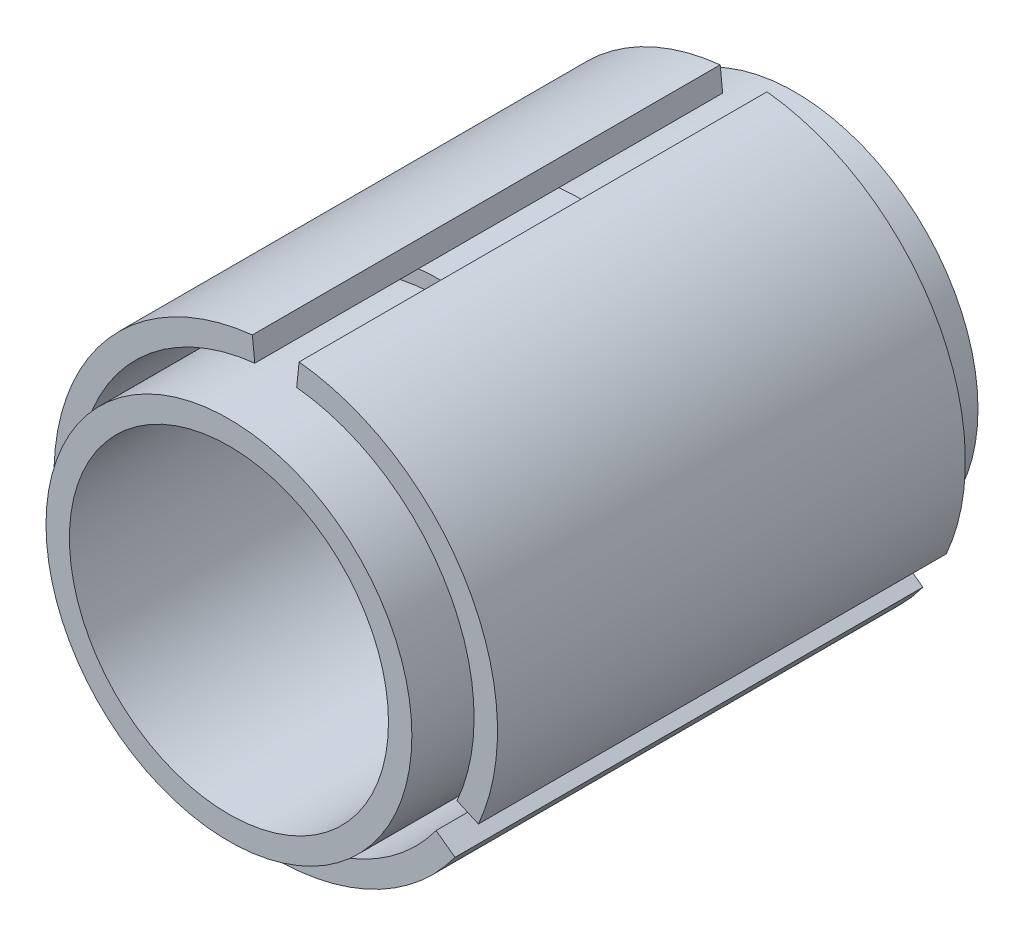
SolidWorks part; units mm, degrees
ref_plane "Alzado" through (0, 0, 0) normal (0, 0, 1) x (1, 0, 0)
ref_plane "Planta" through (0, 0, 0) normal (0, 1, 0) x (1, 0, 0)
ref_plane "Vista lateral" through (0, 0, 0) normal (1, 0, 0) x (0, 0, -1)
sketch "Croquis1" plane through (0, 0, 0) normal (0, 0, 1) x (1, 0, 0)
  circle A0 centre (0, 0) radius 42.4
  dimension "D1" = 84.8
extrude "Saliente-Extruir1" add sketch "Croquis1" along normal mid plane 30
sketch "Croquis2" plane through (0, 0, 0) normal (0, 0, 1) x (1, 0, 0)
  line L0 (0, 0) -> (0, 47.1355) construction
  line L1 (0, 0) -> (-5, 47.1355) construction
  line L2 (0, 0) -> (5, 47.1355) construction
  line L4 (-5, 47.1355) -> (-4.4726, 42.1634)
  line L5 (5, 47.1355) -> (4.4726, 42.1634)
  line L6 (38.3206, -27.8979) -> (34.2783, -24.9551)
  line L7 (43.3206, -19.2376) -> (38.7509, -17.2084)
  line L8 (-43.3206, -19.2376) -> (-38.7509, -17.2084)
  line L9 (-38.3206, -27.8979) -> (-34.2783, -24.9551)
  arc A0 (-5, 47.1355) -> (-43.3206, -19.2376) centre (0, 0) ccw
  circle A1 centre (0, 0) radius 42.4 construction
  arc A2 (-4.4726, 42.1634) -> (-38.7509, -17.2084) centre (0, 0) ccw
  arc A3 (38.7509, -17.2084) -> (4.4726, 42.1634) centre (0, 0) ccw
  arc A4 (43.3206, -19.2376) -> (5, 47.1355) centre (0, 0) ccw
  arc A5 (-38.3206, -27.8979) -> (38.3206, -27.8979) centre (0, 0) ccw
  arc A6 (-34.2783, -24.9551) -> (34.2783, -24.9551) centre (0, 0) ccw
  point P24 (0, 0)
  dimension "D1" = 10
  dimension "D2" = 5
  dimension "D3" = 5
  dimension "D4" = 3
extrude "Saliente-Extruir2" add sketch "Croquis2" along normal mid plane 30
sketch "Croquis3" plane through (0, 0, 0) normal (0, 0, 1) x (1, 0, 0)
  line L0 (-4.4726, 42.1634) -> (-5, 47.1355)
  line L1 (-4.4726, 42.1634) -> (-5, 47.1355) construction
  line L2 (4.4726, 42.1634) -> (5, 47.1355)
  line L3 (38.7509, -17.2084) -> (43.3206, -19.2376)
  line L4 (38.7509, -17.2084) -> (43.3206, -19.2376) construction
  line L5 (38.3206, -27.8979) -> (34.2783, -24.9551)
  line L6 (38.3206, -27.8979) -> (34.2783, -24.9551) construction
  line L7 (-38.3206, -27.8979) -> (-34.2783, -24.9551)
  line L8 (-34.2783, -24.9551) -> (-38.3206, -27.8979) construction
  line L9 (-43.3206, -19.2376) -> (-38.7509, -17.2084)
  line L10 (-43.3206, -19.2376) -> (-38.7509, -17.2084) construction
  arc A0 (-4.4726, 42.1634) -> (-38.7509, -17.2084) centre (0, 0) ccw
  arc A1 (-5, 47.1355) -> (-43.3206, -19.2376) centre (0, 0) ccw
  arc A2 (38.7509, -17.2084) -> (4.4726, 42.1634) centre (0, 0) ccw
  arc A3 (43.3206, -19.2376) -> (5, 47.1355) centre (0, 0) ccw
  arc A4 (-34.2783, -24.9551) -> (34.2783, -24.9551) centre (0, 0) ccw
  arc A5 (-38.3206, -27.8979) -> (38.3206, -27.8979) centre (0, 0) ccw
  dimension "D1" = 84.8
extrude "Saliente-Extruir3" add sketch "Croquis3" along normal mid plane 100
sketch "Croquis4" plane through (0, 0, 0) normal (0, 0, 1) x (1, 0, 0)
  circle A0 centre (0, 0) radius 39.1
  dimension "D1" = 78.2
extrude "Saliente-Extruir4" add sketch "Croquis4" along normal blind 60 and the other way blind 61
sketch "Croquis5" plane through (0, 0, 60) normal (0, 0, 1) x (1, 0, 0)
  circle A0 centre (0, 0) radius 34.1
  dimension "D1" = 68.2
extrude "Cortar-Extruir1" cut sketch "Croquis5" against normal blind 58
sketch "Croquis6" plane through (0, 0, -61) normal (0, 0, -1) x (-1, 0, 0)
  circle A0 centre (0, 0) radius 34.1
  dimension "D1" = 68.2
extrude "Cortar-Extruir2" cut sketch "Croquis6" against normal blind 58
sketch "Croquis7" plane through (0, 0, 0) normal (0, 0, 1) x (1, 0, 0)
  line L0 (5, -5) -> (-5, 5) construction
  line L1 (-5, 5) -> (5, 5) construction
  line L2 (5, 5) -> (-5, -5) construction
  circle A0 centre (5, 5) radius 1.75
  circle A1 centre (-5, 5) radius 1.75
  circle A2 centre (-5, -5) radius 1.75
  circle A3 centre (5, -5) radius 1.75
  point P0 (0, 0)
  point P6 (0, 0)
  dimension "D3" = 3.5
  dimension "D1" = 10
  dimension "D2" = 10
extrude "Cortar-Extruir3" cut sketch "Croquis7" against normal through all both and the other way through all
